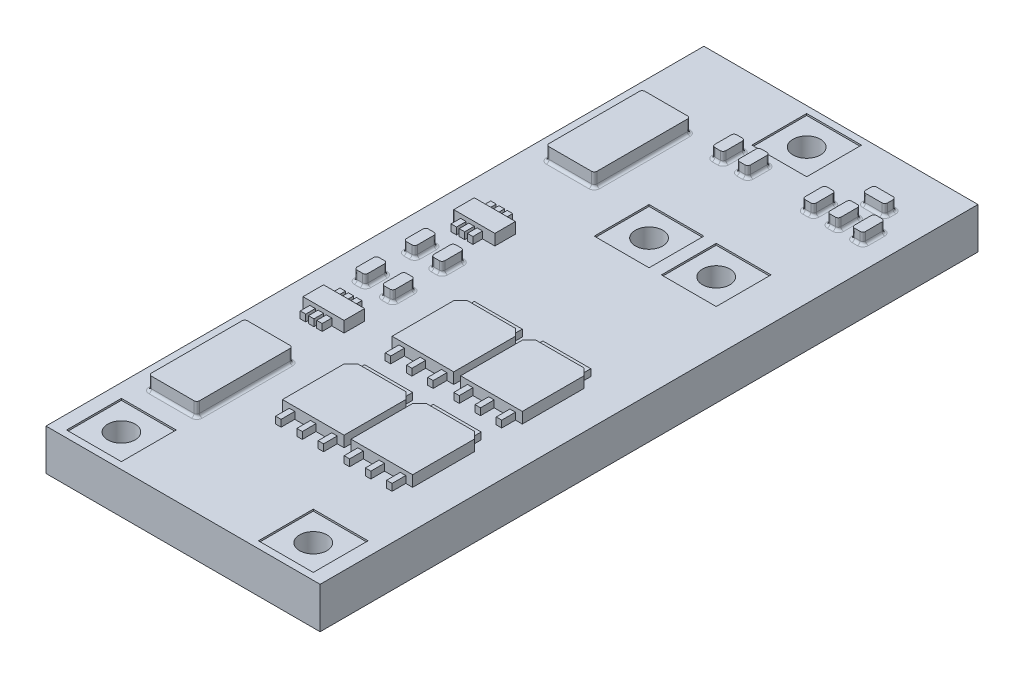
SolidWorks part; units mm, degrees
ref_plane "Alzado" through (0, 0, 0) normal (0, 0, 1) x (1, 0, 0)
ref_plane "Planta" through (0, 0, 0) normal (0, 1, 0) x (1, 0, 0)
ref_plane "Vista lateral" through (0, 0, 0) normal (1, 0, 0) x (0, 0, -1)
sketch "Croquis1" plane through (0, 0, 0) normal (0, 1, 0) x (1, 0, 0)
  line L1 (-10, 24) -> (10, 24)
  line L2 (-10, 24) -> (-10, -24)
  line L3 (-10, -24) -> (10, -24)
  line L4 (10, 24) -> (10, -24)
  line L5 (-10, 24) -> (10, -24) construction
  line L6 (-10, -24) -> (10, 24) construction
  point P0 (0, 0)
  dimension "D1" = 20
  dimension "D2" = 48
extrude "Saliente-Extruir1" add sketch "Croquis1" along normal blind 3
sketch "Croquis2" plane through (0, 3, 0) normal (0, 1, 0) x (1, 0, 0)
  line L0 (-5.1, 1.6) -> (-5.1, 0)
  line L1 (-7.9, 1.6) -> (-7.1, 1.6)
  line L2 (-7.9, 1.6) -> (-7.9, 0)
  line L3 (-7.9, 0) -> (-7.1, 0)
  line L4 (-7.1, 1.6) -> (-7.1, 0)
  line L5 (-7.9, 1.6) -> (-7.1, 0) construction
  line L6 (-7.9, 0) -> (-7.1, 1.6) construction
  line L7 (-7.9, -2) -> (-7.1, -2)
  line L8 (-7.9, -2) -> (-7.9, -3.6)
  line L9 (-7.9, -3.6) -> (-7.1, -3.6)
  line L10 (-7.1, -2) -> (-7.1, -3.6)
  line L11 (-7.9, -2) -> (-7.1, -3.6) construction
  line L12 (-7.9, -3.6) -> (-7.1, -2) construction
  line L13 (-5.9, 1.6) -> (-5.1, 1.6)
  line L14 (-5.9, 1.6) -> (-5.9, 0)
  line L15 (-5.9, 0) -> (-5.1, 0)
  line L16 (-5.9, -2) -> (-5.1, -2)
  line L17 (-5.9, -2) -> (-5.9, -3.6)
  line L18 (-5.1, -2) -> (-5.1, -3.6)
  line L19 (-5.9, -3.6) -> (-5.1, -3.6)
  line L21 (-1.8, 18.8) -> (-2.6, 18.8)
  line L22 (-1.8, 18.8) -> (-1.8, 17.2)
  line L23 (-1.8, 17.2) -> (-2.6, 17.2)
  line L24 (-2.6, 18.8) -> (-2.6, 17.2)
  line L25 (-1.8, 18.8) -> (-2.6, 17.2) construction
  line L26 (-1.8, 17.2) -> (-2.6, 18.8) construction
  line L27 (-0.8, 18.8) -> (0, 18.8)
  line L28 (-0.8, 18.8) -> (-0.8, 17.2)
  line L29 (-0.8, 17.2) -> (0, 17.2)
  line L30 (0, 18.8) -> (0, 17.2)
  line L31 (-0.8, 18.8) -> (0, 17.2) construction
  line L32 (-0.8, 17.2) -> (0, 18.8) construction
  line L33 (4, 18.8) -> (4.8, 18.8)
  line L34 (4, 18.8) -> (4, 17.2)
  line L35 (4, 17.2) -> (4.8, 17.2)
  line L36 (4.8, 18.8) -> (4.8, 17.2)
  line L37 (4, 18.8) -> (4.8, 17.2) construction
  line L38 (4, 17.2) -> (4.8, 18.8) construction
  line L39 (5.8, 18.8) -> (6.6, 18.8)
  line L40 (5.8, 18.8) -> (5.8, 17.2)
  line L41 (5.8, 17.2) -> (6.6, 17.2)
  line L42 (6.6, 18.8) -> (6.6, 17.2)
  line L43 (5.8, 18.8) -> (6.6, 17.2) construction
  line L44 (5.8, 17.2) -> (6.6, 18.8) construction
  line L45 (5.8, 20.6) -> (7.4, 20.6)
  line L46 (5.8, 20.6) -> (5.8, 19.8)
  line L47 (5.8, 19.8) -> (7.4, 19.8)
  line L48 (7.4, 20.6) -> (7.4, 19.8)
  line L49 (5.8, 20.6) -> (7.4, 19.8) construction
  line L50 (5.8, 19.8) -> (7.4, 20.6) construction
  line L51 (7.6, 18.8) -> (8.4, 18.8)
  line L52 (7.6, 18.8) -> (7.6, 17.2)
  line L53 (7.6, 17.2) -> (8.4, 17.2)
  line L54 (8.4, 18.8) -> (8.4, 17.2)
  line L55 (7.6, 18.8) -> (8.4, 17.2) construction
  line L56 (7.6, 17.2) -> (8.4, 18.8) construction
  point P0 (-7.5, 0.8)
  point P5 (-7.5, -2.8)
  point P10 (-0.4, 18)
  point P21 (-2.2, 18)
  point P29 (4.4, 18)
  point P34 (6.2, 18)
  point P39 (6.6, 20.2)
  point P44 (8, 18)
  dimension "D1" = 0.8
  dimension "D2" = 0.8
  dimension "D3" = 1.6
  dimension "D4" = 1.6
  dimension "D6" = 2
  dimension "D7" = 7.5
  dimension "D8" = 1
  dimension "D9" = 0.8
  dimension "D10" = 0.8
  dimension "D11" = 1.6
  dimension "D12" = 1.6
  dimension "D13" = 1.6
  dimension "D14" = 1.6
  dimension "D15" = 1.6
  dimension "D16" = 0.8
  dimension "D17" = 0.8
  dimension "D18" = 0.8
  dimension "D19" = 1.6
  dimension "D20" = 0.8
  dimension "D21" = 1
  dimension "D22" = 1
  dimension "D23" = 4
  dimension "D24" = 1
  dimension "D25" = 18
  dimension "D5" = 2
extrude "Saliente-Extruir2" add sketch "Croquis2" along normal blind 0.8
fillet "Redondeo1" radius 0.2 80 edges at (-0.4, 3, -17.2) (-5.9, 3, 2.8) (-7.9, 3, 2.8) (-7.9, 3, -0.8) (-5.5, 3, -1.6) (8.4, 3, -18) (7.4, 3, -20.2) (5.8, 3, -18) (4, 3, -18) (-2.6, 3, -18) (0, 3, -18) (-0.8, 3, -18) (-5.5, 3, 3.6) (-5.5, 3, 2) (-7.5, 3, 3.6) (-7.5, 3, 2) (-7.5, 3, 0) (-7.5, 3, -1.6) (-5.9, 3, -0.8) (-5.1, 3, -0.8) (8, 3, -18.8) (8, 3, -17.2) (6.6, 3, -20.6) (6.6, 3, -19.8) (6.2, 3, -17.2) (6.2, 3, -18.8) (4.4, 3, -17.2) (4.4, 3, -18.8) (-2.2, 3, -17.2) (-2.2, 3, -18.8) (-0.4, 3, -18.8) (-0.8, 3.4, -18.8) (0, 3.4, -18.8) (-5.1, 3, 2.8) (-5.9, 3.4, 2) (-5.1, 3.4, 2) (-5.9, 3.4, 3.6) (-5.1, 3.4, 3.6) (-7.1, 3, 2.8) (-7.1, 3.4, 2) (-7.1, 3.4, 3.6) (-7.9, 3.4, 2) (-7.9, 3.4, 3.6) (-7.1, 3, -0.8) (-7.1, 3.4, -1.6) (-7.1, 3.4, 0) (-7.9, 3.4, -1.6) (-7.9, 3.4, 0) (-5.9, 3.4, 0) (-5.5, 3, 0) (-5.9, 3.4, -1.6) (-5.1, 3.4, 0) (-5.1, 3.4, -1.6) (7.6, 3, -18) (7.6, 3.4, -18.8) (7.6, 3.4, -17.2) (8.4, 3.4, -17.2) (8.4, 3.4, -18.8) (5.8, 3, -20.2) (5.8, 3.4, -19.8) (5.8, 3.4, -20.6) (7.4, 3.4, -20.6) (7.4, 3.4, -19.8) (5.8, 3.4, -18.8) (6.6, 3, -18) (6.6, 3.4, -18.8) (5.8, 3.4, -17.2) (6.6, 3.4, -17.2) (4.8, 3, -18) (4, 3.4, -18.8) (4.8, 3.4, -18.8) (4, 3.4, -17.2) (4.8, 3.4, -17.2) (-1.8, 3, -18) (0, 3.4, -17.2) (-0.8, 3.4, -17.2) (-1.8, 3.4, -17.2) (-2.6, 3.4, -17.2) (-2.6, 3.4, -18.8) (-1.8, 3.4, -18.8)
sketch "Croquis3" plane through (0, 3, 0) normal (0, 1, 0) x (1, 0, 0)
  line L0 (10, 24) -> (-10, 24) construction
  line L1 (-8.5, 18) -> (-5, 18)
  line L2 (-8.5, 18) -> (-8.5, 11)
  line L3 (-8.5, 11) -> (-5, 11)
  line L4 (-5, 18) -> (-5, 11)
  line L5 (-8.5, 18) -> (-5, 11) construction
  line L6 (-8.5, 11) -> (-5, 18) construction
  line L7 (-8.5, -11) -> (-5, -11)
  line L8 (-8.5, -11) -> (-8.5, -18)
  line L9 (-8.5, -18) -> (-5, -18)
  line L10 (-5, -11) -> (-5, -18)
  line L11 (-8.5, -11) -> (-5, -18) construction
  line L12 (-8.5, -18) -> (-5, -11) construction
  line L13 (-10, -24) -> (10, -24) construction
  line L14 (-10, 24) -> (-10, -24) construction
  point P0 (-6.75, 14.5)
  point P5 (-6.75, -14.5)
  point P16 (-6.75, 19)
  dimension "D1" = 6
  dimension "D2" = 6
  dimension "D3" = 1.5
  dimension "D4" = 7
  dimension "D5" = 3.5
  dimension "D6" = 7
  dimension "D7" = 3.5
extrude "Saliente-Extruir3" add sketch "Croquis3" along normal blind 1
fillet "Redondeo2" radius 0.2 16 edges at (-6.75, 3, 11) (-6.75, 3, -18) (-5, 3, 14.5) (-8.5, 3, 14.5) (-8.5, 3, -14.5) (-5, 3, -14.5) (-8.5, 3.5, 11) (-5, 3.5, 11) (-5, 3.5, 18) (-8.5, 3.5, 18) (-6.75, 3, 18) (-6.75, 3, -11) (-5, 3.5, -11) (-5, 3.5, -18) (-8.5, 3.5, -11) (-8.5, 3.5, -18)
sketch "Croquis4" plane through (0, 3, 0) normal (0, 1, 0) x (1, 0, 0)
  line L0 (1.75, -1.5) -> (2.25, -2)
  line L1 (-1.75, -1.5) -> (1.75, -1.5)
  line L2 (-2.25, -2) -> (-2.25, -6.5)
  line L3 (-2.25, -6.5) -> (2.25, -6.5)
  line L4 (2.25, -2) -> (2.25, -6.5)
  line L5 (-2.25, -1.5) -> (2.25, -6.5) construction
  line L6 (-2.25, -6.5) -> (2.25, -1.5) construction
  line L7 (10, -24) -> (10, 24) construction
  line L8 (-10, -24) -> (10, -24) construction
  line L9 (-1.75, -1.5) -> (-2.25, -2)
  point P0 (0, -4)
  dimension "D1" = 4.5
  dimension "D2" = 5
  dimension "D3" = 10
  dimension "D4" = 20
extrude "Saliente-Extruir4" add sketch "Croquis4" along normal blind 0.8
sketch "Croquis5" plane through (0, 3, 0) normal (0, 1, 0) x (1, 0, 0)
  line L0 (1.75, -1.5) -> (-1.75, -1.5) construction
  line L1 (1.75, -1.5) -> (-1.75, -1.5)
  line L2 (-1.75, -1.5) -> (-1.75, -1)
  line L3 (-1.75, -1) -> (1.75, -1)
  line L4 (1.75, -1) -> (1.75, -1.5)
  line L5 (-1.75, -6.5) -> (-1.75, -7.4986)
  line L6 (-2.25, -6.5) -> (2.25, -6.5) construction
  line L7 (-1.75, -7.4986) -> (-1.35, -7.4986)
  line L8 (-1.35, -7.4986) -> (-1.35, -6.5)
  line L9 (-1.35, -6.5) -> (-1.75, -6.5)
  line L13 (1.35, -7.5) -> (1.35, -6.5)
  line L14 (-2.25, -6.5) -> (2.25, -6.5) construction
  line L15 (1.35, -6.5) -> (1.75, -6.5)
  line L16 (1.75, -6.5) -> (1.75, -7.5)
  line L17 (1.75, -7.5) -> (1.35, -7.5)
  line L19 (-1.35, -6.5) -> (-1.75, -6.5)
  line L21 (2.25, -6.5) -> (2.25, -2) construction
  line L23 (-0.2027, -6.5) -> (0.1973, -6.5)
  line L24 (-0.2027, -6.5) -> (-0.2027, -7.4986)
  line L25 (-0.2027, -7.4986) -> (0.1973, -7.4986)
  line L26 (0.1973, -6.5) -> (0.1973, -7.4986)
  line L27 (-0.2027, -6.5) -> (0.1973, -7.4986) construction
  line L28 (-0.2027, -7.4986) -> (0.1973, -6.5) construction
  point P8 (-0.0027, -6.9993)
  point P18 (0, 0)
  dimension "D1" = 0.5
  dimension "D2" = 0.4
  dimension "D3" = 1.1527
  dimension "D4" = 0.4
  dimension "D5" = 1
  dimension "D6" = 0.5
  dimension "D7" = 0.4
  dimension "D8" = 0.9986
extrude "Saliente-Extruir5" add sketch "Croquis5" along normal blind 0.5 contours L8 L9 L5 L7 | L4 L3 L2 L1 | L25 L26 L23 L24 | L13 L15 L16 L17 region at (0, 3, 1.25) region at (-1.55, 3, 6.9993)
pattern_linear "MatrizL1" count 2 spacing 5 along (1, 0, 0) count 2 spacing 8 along (0, 0, 1) of "Saliente-Extruir5", "Saliente-Extruir4"
sketch "Croquis6" plane through (0, 3, 0) normal (0, 1, 0) x (1, 0, 0)
  line L0 (-10, 24) -> (-10, -24) construction
  line L1 (-9, -19.5) -> (-5, -19.5)
  line L2 (-9, -19.5) -> (-9, -23.5)
  line L3 (-9, -23.5) -> (-5, -23.5)
  line L4 (-5, -19.5) -> (-5, -23.5)
  line L5 (-9, -19.5) -> (-5, -23.5) construction
  line L6 (-9, -23.5) -> (-5, -19.5) construction
  line L7 (5, -19.5) -> (9, -19.5)
  line L8 (9, -19.5) -> (9, -23.5)
  line L9 (5, -19.5) -> (5, -23.5)
  line L10 (5, -23.5) -> (9, -23.5)
  line L11 (10, -24) -> (10, 24) construction
  line L12 (-10, -24) -> (10, -24) construction
  circle A0 centre (-7, -21.5) radius 1
  circle A1 centre (7, -21.5) radius 1
  point P0 (-7, -21.5)
  dimension "D1" = 2
  dimension "D2" = 4
  dimension "D3" = 4
  dimension "D4" = 1
  dimension "D6" = 1
  dimension "D7" = 2.5
  dimension "D5" = 2
extrude "Cortar-Extruir1" cut sketch "Croquis6" against normal blind 0.125
extrude "Cortar-Extruir2" cut sketch "Croquis6<2>" against normal up to surface (3 mm away) contours A0 | A1 region at (-7, 3, 21.5) region at (7, 3, 21.5) up to face at (0, 0, 0)
sketch "Croquis6<2>" plane through (0, 3, 0) normal (0, 1, 0) x (1, 0, 0) same geometry as "Croquis6"
sketch "Croquis8" plane through (0, 3, 0) normal (0, 1, 0) x (1, 0, 0)
  line L0 (-10, 24) -> (-10, -24) construction
  line L1 (-8, -5.75) -> (-5, -5.75)
  line L2 (-8, -5.75) -> (-8, -7.25)
  line L3 (-8, -7.25) -> (-5, -7.25)
  line L4 (-5, -5.75) -> (-5, -7.25)
  line L5 (-8, -5.75) -> (-5, -7.25) construction
  line L6 (-8, -7.25) -> (-5, -5.75) construction
  line L7 (-5, 5.25) -> (-5, 3.75)
  line L8 (-8, 5.25) -> (-5, 5.25)
  line L9 (-8, 3.75) -> (-5, 3.75)
  line L10 (-8, 5.25) -> (-8, 3.75)
  point P0 (-6.5, -6.5)
  dimension "D1" = 3
  dimension "D2" = 1.5
  dimension "D3" = 3.5
  dimension "D4" = 6.5
  dimension "D5" = 2
extrude "Saliente-Extruir6" add sketch "Croquis8" along normal up to surface (0.8 mm away) up to face at (0, 3.8, 3.3333)
sketch "Croquis9" plane through (0, 3, 0) normal (0, 1, 0) x (1, 0, 0)
  line L0 (-7.5, -5.75) -> (-7.5, -5.05)
  line L1 (-7.5, -5.05) -> (-7.1, -5.05)
  line L2 (-7.1, -5.05) -> (-7.1, -5.75)
  line L3 (-7.1, -5.75) -> (-6.9, -5.75)
  line L4 (-8, -7.25) -> (-5, -7.25)
  line L5 (-5, -7.25) -> (-5, -5.75)
  line L6 (-5, -5.75) -> (-8, -5.75)
  line L7 (-8, -5.75) -> (-8, -7.25)
  line L8 (-8, -7.25) -> (-5, -7.25)
  line L10 (-5, -5.75) -> (-8, -5.75)
  line L12 (-6.9, -5.75) -> (-6.9, -5.05)
  line L13 (-6.9, -5.05) -> (-6.5, -5.05)
  line L14 (-6.5, -5.05) -> (-6.5, -5.75)
  line L15 (-6.5, -5.75) -> (-6.3, -5.75)
  line L16 (-6.3, -5.75) -> (-6.3, -5.05)
  line L17 (-6.3, -5.05) -> (-5.9, -5.05)
  line L18 (-5.9, -5.05) -> (-5.9, -5.75)
  line L19 (-7.5, -7.25) -> (-7.5, -7.95)
  line L20 (-7.5, -7.95) -> (-7.1, -7.95)
  line L21 (-7.1, -7.95) -> (-7.1, -7.25)
  line L22 (-6.9, -7.25) -> (-6.9, -7.95)
  line L23 (-6.9, -7.95) -> (-6.5, -7.95)
  line L24 (-6.5, -7.95) -> (-6.5, -7.25)
  line L25 (-6.3, -7.25) -> (-6.3, -7.95)
  line L26 (-6.3, -7.95) -> (-5.9, -7.95)
  line L27 (-5.9, -7.95) -> (-5.9, -7.25)
  line L28 (-8, -5.75) -> (-8, -7.25) construction
  line L29 (-5, -7.25) -> (-5, -5.75) construction
  line L30 (-8, -5.75) -> (-8, -7.25)
  line L31 (-5, -7.25) -> (-5, -5.75)
  point P38 (-6.7, -7.95)
  point P39 (-6.7, -5.05)
  point P40 (-6.1, -7.95)
  point P41 (-6.1, -5.05)
  dimension "D2" = 0.5
  dimension "D3" = 0.4
  dimension "D4" = 0.4
  dimension "D5" = 0.9
  dimension "D6" = 0.4
  dimension "D7" = 0.7
  dimension "D8" = 0.4
  dimension "D9" = 0.4
  dimension "D10" = 0.4
  dimension "D11" = 0.7
  dimension "D1" = 0
extrude "Saliente-Extruir7" add sketch "Croquis9" along normal up to surface (0.5 mm away) contours L10 L2 L1 L0 | L14 L13 L12 L10 | L18 L17 L16 L10 | L26 L27 L8 L25 | L23 L24 L8 L22 | L20 L21 L8 L19 region at (-7.3, 3, 5.4) region at (-6.7, 3, 5.4) region at (-7.3, 3, 7.6) region at (-6.1, 3, 5.4) region at (-6.7, 3, 7.6) region at (-6.1, 3, 7.6) up to face at (-1.55, 3.5, 6.9993)
pattern_linear "MatrizL2" count 2 spacing 11 along (0, 0, -1) of "Saliente-Extruir7"
sketch "Croquis10" plane through (0, 3, 0) normal (0, 1, 0) x (1, 0, 0)
  line L0 (10, 24) -> (-10, 24) construction
  line L1 (-2, 23.5) -> (2, 23.5)
  line L2 (-2, 23.5) -> (-2, 19.5)
  line L3 (-2, 19.5) -> (2, 19.5)
  line L4 (2, 23.5) -> (2, 19.5)
  line L5 (-2, 23.5) -> (2, 19.5) construction
  line L6 (-2, 19.5) -> (2, 23.5) construction
  circle A0 centre (0, 21.5) radius 1
  point P0 (0, 21.5)
  point P9 (0, 0)
  dimension "D4" = 2
  dimension "D1" = 0.5
  dimension "D2" = 4
  dimension "D3" = 4
extrude "Cortar-Extruir3" cut sketch "Croquis10" against normal blind 0.125 contours L4 L1 L2 L3 A0 region at (0, 3, -23.4434)
extrude "Cortar-Extruir4" cut sketch "Croquis10<3>" against normal up to surface (3 mm away) contours A0 region at (0, 3, -21.5) up to face at (-7, 0, 22.5)
sketch "Croquis10<3>" plane through (0, 3, 0) normal (0, 1, 0) x (1, 0, 0) same geometry as "Croquis10"
sketch "Croquis11" plane through (0, 3, 0) normal (0, 1, 0) x (1, 0, 0)
  line L1 (-2, 12) -> (2, 12)
  line L2 (-2, 12) -> (-2, 8)
  line L3 (-2, 8) -> (2, 8)
  line L4 (2, 12) -> (2, 8)
  line L5 (-2, 12) -> (2, 8) construction
  line L6 (-2, 8) -> (2, 12) construction
  circle A0 centre (0, 10) radius 1
  point P0 (0, 10)
  dimension "D4" = 2
  dimension "D1" = 4
  dimension "D2" = 4
  dimension "D3" = 10
extrude "Cortar-Extruir5" cut sketch "Croquis11" against normal blind 0.125
extrude "Cortar-Extruir7" cut sketch "Croquis11<2>" against normal up to surface (3 mm away) contours A0 region at (0, 3, -10) up to face at (0, 0, -20.5)
sketch "Croquis11<2>" plane through (0, 3, 0) normal (0, 1, 0) x (1, 0, 0) same geometry as "Croquis11"
pattern_linear "MatrizL3" count 2 spacing 4.9 along (1, 0, 0) of "Cortar-Extruir5", "Cortar-Extruir7"
